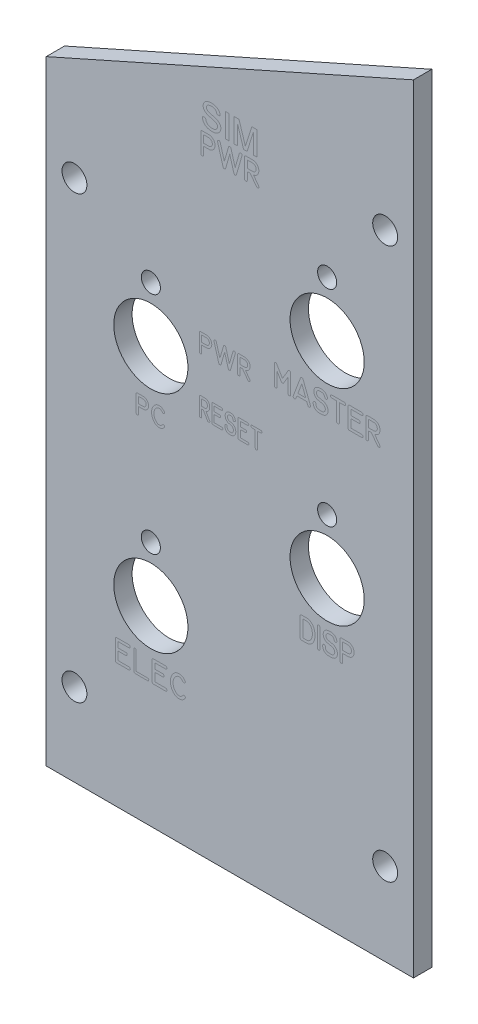
SolidWorks part; units mm, degrees
material "PET"
ref_plane "Front Plane" through (0, 0, 0) normal (0, 0, 1) x (1, 0, 0)
ref_plane "Top Plane" through (0, 0, 0) normal (0, 1, 0) x (1, 0, 0)
ref_plane "Right Plane" through (0, 0, 0) normal (1, 0, 0) x (0, 0, -1)
sketch "Sketch1" plane through (0, 0, 0) normal (0, 0, 1) x (1, 0, 0)
  line L4 (0, 107.95) -> (0, 0)
  line L5 (0, 0) -> (63.5, 0)
  line L6 (63.5, 0) -> (63.5, 136.2202)
  line L7 (63.5, 136.2202) -> (0, 107.95)
  line L8 (0, 107.95) -> (0, 0)
  line L9 (0, 0) -> (63.5, 0)
  line L10 (63.5, 0) -> (63.5, 136.2202)
  line L11 (63.5, 136.2202) -> (0, 107.95)
  dimension "D1" = 0
extrude "Boss-Extrude1" add sketch "Sketch1" against normal blind 3.175
sketch "Sketch2" plane through (0, 0, 0) normal (0, 0, 1) x (1, 0, 0)
  circle A0 centre (48.5775, 52.3875) radius 6.4135 construction
  circle A1 centre (48.5775, 61.9125) radius 1.651 construction
  circle A2 centre (48.5775, 87.9475) radius 6.4135 construction
  circle A3 centre (48.5775, 97.4725) radius 1.651 construction
  circle A4 centre (18.0975, 81.4387) radius 1.651 construction
  circle A5 centre (18.0975, 71.9137) radius 6.4135 construction
  circle A6 centre (18.0975, 42.545) radius 1.651 construction
  circle A7 centre (18.0975, 33.02) radius 6.4135 construction
  circle A8 centre (41.275, 22.225) radius 1.651 construction
  circle A9 centre (41.275, 12.7) radius 6.4135 construction
  circle A10 centre (48.5775, 52.3875) radius 6.4135
  circle A11 centre (48.5775, 61.9125) radius 1.651
  circle A12 centre (48.5775, 87.9475) radius 6.4135
  circle A13 centre (48.5775, 97.4725) radius 1.651
  circle A14 centre (18.0975, 81.4387) radius 1.651
  circle A15 centre (18.0975, 71.9137) radius 6.4135
  circle A16 centre (18.0975, 42.545) radius 1.651
  circle A17 centre (18.0975, 33.02) radius 6.4135
  circle A18 centre (41.275, 22.225) radius 1.651 construction
  circle A19 centre (41.275, 12.7) radius 6.4135 construction
extrude "Cut-Extrude1" cut sketch "Sketch2" against normal through all
hole_wizard "#6 Clearance Hole1" positions "Sketch4" profile "Sketch3" hole size "#6" standard "ANSI Inch" end condition through all
sketch "Sketch4" plane through (0, 0, 0) normal (0, 0, 1) x (1, 0, 0)
  point P0 (58.6105, 14.2875)
  point P3 (4.8895, 14.2875)
  point P6 (4.8895, 90.4875)
  point P9 (58.6105, 109.5375)
sketch "Sketch3" plane through (58.6105, 14.2875, 0) normal (1, 0, 0) x (0, -1, 0)
  line L0 (0, 0) -> (0, 3.175)
  line L1 (0, 3.175) -> (2.1526, 3.175)
  line L2 (2.1526, 3.175) -> (2.1526, 0)
  line L5 (2.1526, 0) -> (0, 0)
  line L11 (0, -6.35) -> (0, 107.95) construction
  dimension "Thru Hole Dia." = 4.3053
  dimension "Thru Hole Depth" = 3.175
sketch "Sketch5" plane through (0, 0, 0) normal (0, 0, 1) x (1, 0, 0)
  line L0 (31.75, 122.0851) -> (31.75, 109.3851) construction
  line L1 (26.289, 75.0725) -> (38.1394, 75.0725) construction
  line L2 (31.75, 109.3851) -> (31.75, 104.8131) construction
  line L3 (18.2215, 109.3851) -> (45.2785, 109.3851) construction
  line L4 (18.2215, 104.8131) -> (45.2785, 104.8131) construction
  line L5 (18.0975, 65.5002) -> (18.0975, 60.4202) construction
  line L6 (6.4775, 60.4202) -> (29.7175, 60.4203) construction
  line L8 (18.0975, 26.6065) -> (18.0975, 21.5265) construction
  line L10 (6.4775, 21.5265) -> (29.7175, 21.5265) construction
  line L11 (26.3024, 65.5002) -> (38.1528, 65.5002) construction
  line L13 (18.0975, 65.5002) -> (26.3024, 65.5002) construction
  line L14 (48.5775, 45.974) -> (48.5775, 40.894) construction
  line L15 (38.1394, 40.894) -> (59.0156, 40.894) construction
  line L16 (38.1394, 76.454) -> (59.0156, 76.454) construction
  line L17 (56.769, 87.9475) -> (56.769, 86.1695) construction
  line L18 (56.769, 86.1695) -> (62.9952, 86.1695) construction
  line L19 (54.991, 87.9475) -> (56.769, 87.9475) construction
  line L20 (48.5775, 81.534) -> (48.5775, 76.454) construction
  circle A0 centre (18.0975, 71.9137) radius 6.4135 construction
  circle A1 centre (18.0975, 33.02) radius 6.4135 construction
  text T0 "SIM" height in points 16
  text T1 "PWR" font "GordonURWMed" height in points 16
  text T2 "PC" font "GordonURWMed" height in points 14
  text T3 "ELEC" font "GordonURWMed" height in points 16
  text T4 "PWR" font "GordonURWMed" height in points 14
  text T5 "DISP" font "GordonURWMed" height in points 16
  text T6 "MASTER" font "GordonURWMed" height in points 16
  text T7 "RESET" font "GordonURWCon" height in points 14
  point P9 (31.75, 109.3851)
  point P12 (31.75, 104.8131)
  point P26 (18.0975, 60.4202)
  point P31 (18.0975, 21.5265)
  point P43 (48.5775, 40.894)
  point P47 (48.5775, 76.454)
  dimension "D1" = 4.572
  dimension "D2" = 12.7
  dimension "D5" = 5.08
wrap "Wrap1" sketch "Sketch5" wrap type scribe source sketch "Sketch5" face at (60.7631, 14.2875, 0)
sketch "Sketch6" plane through (0, 0, 0) normal (0, 0, 1) x (1, 0, 0)
  line L0 (63.5, 136.2202) -> (0, 107.95) construction
  line L1 (63.5, 136.2202) -> (0, 107.95)
  line L2 (63.5, 134.4825) -> (0, 106.2123)
  line L3 (64.1457, 134.7699) -> (0.6457, 106.4997) construction
  line L4 (63.5, 0) -> (63.5, 136.2202) construction
  line L5 (0, 107.95) -> (0, 0) construction
  line L6 (0, 107.95) -> (0, 106.2123)
  line L7 (63.5, 136.2202) -> (63.5, 134.4825)
  dimension "D1" = 1.5875
extrude "Cut-Extrude2" cut sketch "Sketch6" against normal through all
